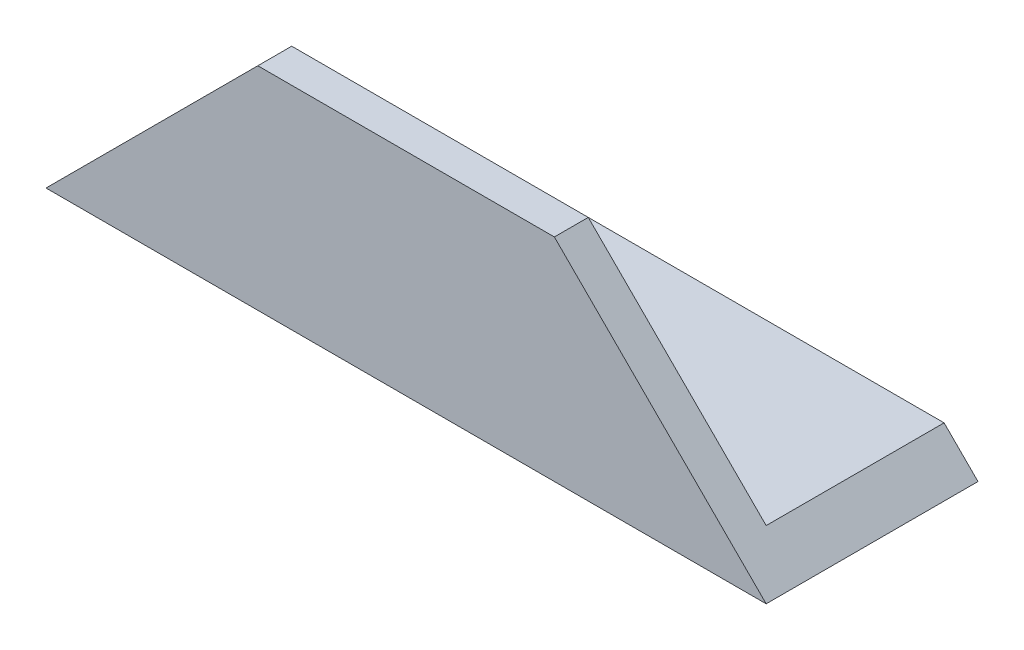
SolidWorks part; units mm, degrees
ref_plane "Спереди" through (0, 0, 0) normal (0, 0, 1) x (1, 0, 0)
ref_plane "Сверху" through (0, 0, 0) normal (0, 1, 0) x (1, 0, 0)
ref_plane "Справа" through (0, 0, 0) normal (1, 0, 0) x (0, 0, -1)
sketch "Эскиз1" plane through (0, 0, 0) normal (1, 0, 0) x (0, 0, -1)
  line L0 (0, 0) -> (25, 0)
  line L1 (0, 0) -> (0, 25)
extrude "Вытянуть-Тонкостенный1" add sketch "Эскиз1" along normal blind 85 thin thin type one direction wall 4
sketch "Эскиз2" plane through (0, 0, 0) normal (0, 0, 1) x (1, 0, 0)
  line L0 (0, 0) -> (0, 25)
  line L1 (0, 25) -> (25, 25)
  line L2 (85, 25) -> (0, 25) construction
  line L3 (25, 25) -> (0, 0)
  line L4 (85, 0) -> (0, 0) construction
  line L5 (60, 25) -> (85, 25)
  line L6 (85, 25) -> (85, 0)
  line L7 (85, 0) -> (85, 25) construction
  line L9 (85, 0) -> (60, 25)
extrude "Вырез-Вытянуть1" cut sketch "Эскиз2" against normal through all
sketch "Эскиз3" plane through (0, 0, 0) normal (0, -1, 0) x (1, 0, 0)
  line L1 (0, -25) -> (32, -25)
  line L2 (0, -25) -> (0, -4)
  line L3 (0, -4) -> (32, -4)
  line L4 (32, -25) -> (32, -4)
extrude "Вырез-Вытянуть2" cut sketch "Эскиз3" against normal blind 10
